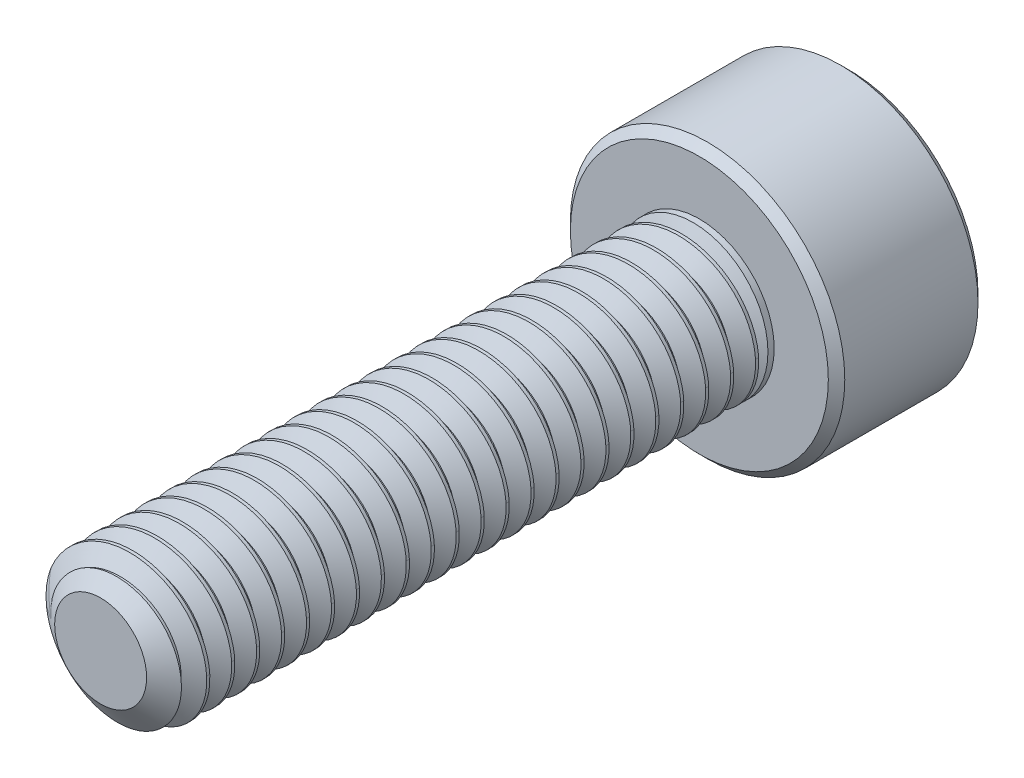
SolidWorks part; units mm, degrees
material "Cast Alloy Steel"
ref_plane "Front Plane" through (0, 0, 0) normal (0, 0, 1) x (1, 0, 0)
ref_plane "Top Plane" through (0, 0, 0) normal (0, 1, 0) x (1, 0, 0)
ref_plane "Right Plane" through (0, 0, 0) normal (1, 0, 0) x (0, 0, -1)
sketch "Sketch1" plane through (0, 0, 0) normal (0, 0, 1) x (1, 0, 0)
  circle A0 centre (0, 0) radius 1.5
  dimension "OD" = 3
extrude "Extrude1" add sketch "Sketch1" against normal blind 12
sketch "Sketch2" plane through (0, 0, 0) normal (0, 0, 1) x (1, 0, 0)
  circle A0 centre (0, 0) radius 1.5 construction
  circle A1 centre (0, 0) radius 1.5
curve "Helix/Spiral1" pitch 0.5 height 12.5 radius 1.5 centre (0, 0, 0) axis (0, 0, -1) start towards (0, 1, 0) parameters "pitch"=0.5
sketch "Sketch3" plane through (0, 0, 0) normal (1, 0, 0) x (0, 0, -1)
  line L0 (-0.4375, 1.5) -> (-0.25, 1.1752)
  line L1 (-0.25, 1.1752) -> (-0.1875, 1.1752)
  line L2 (-0.1875, 1.1752) -> (0, 1.5)
  line L3 (-0.4375, 1.5) -> (0, 1.5)
  line L4 (-0.2187, 1.5) -> (-0.2187, 1.1752) construction
  line L5 (-0.3437, 1.3376) -> (-0.0937, 1.3376) construction
  line L6 (0, 1.5) -> (0, -1.5) construction
  line L7 (0, -1.5) -> (12, -1.5) construction
  point P11 (2.25, -1.5)
  dimension "D1" = 0.0625
  dimension "D2" = 0.25
  dimension "D3" = 60
  dimension "D4" = 2.25
sweep "Cut-Sweep1" cut profiles "Sketch3" path "Helix/Spiral1" align with end faces yes
sketch "Sketch4" plane through (0, 0, 0) normal (1, 0, 0) x (0, 0, -1)
  line L0 (0.4053, 1.5) -> (0, 0.9212)
  line L1 (0, 0.9212) -> (0, 1.5)
  line L2 (0.4053, 1.5) -> (0, 1.5)
  line L3 (-0.4375, 1.5) -> (0, 1.5) construction
  line L4 (0, 0) -> (7.0209, 0) construction
  dimension "D1" = 55
  dimension "D2" = 0.254
revolve "Cut-Revolve1" cut sketch "Sketch4" angle 360 about L4
sketch "Sketch5" plane through (0, 0, 0) normal (1, 0, 0) x (0, 0, -1)
  line L0 (12, -1.1822) -> (12, 1.0703) construction
  line L1 (12, 1.5) -> (0.1203, 1.5)
  line L2 (12, 1.5) -> (12, 0)
  line L3 (12, 0) -> (0.0001, 0)
  line L4 (0.0001, 1.1698) -> (0.0001, 0)
  line L5 (0.1203, 1.5) -> (0.0001, 1.1698)
  line L6 (0, 0) -> (9.9695, 0) construction
  point P3 (0.0001, 1.5)
  point P10 (0.0001, 1.5)
  dimension "D1" = 0.3302
  dimension "Thread min" = 0.0001
  dimension "D3" = 20
revolve "partially thread" [suppressed] add sketch "Sketch5" angle 360 about L6
sketch "Sketch6" plane through (0, 0, -12) normal (0, 0, -1) x (-1, 0, 0)
  circle A0 centre (0, 0) radius 2.75
  dimension "head dia" = 5.5
extrude "Extrude2" add sketch "Sketch6" along normal blind 3
sketch "Sketch7" plane through (0, 0, -15) normal (0, 0, -1) x (-1, 0, 0)
  line L1 (0, 1.4434) -> (-1.25, 0.7217)
  line L2 (-1.25, 0.7217) -> (-1.25, -0.7217)
  line L3 (-1.25, -0.7217) -> (0, -1.4434)
  line L4 (0, -1.4434) -> (1.25, -0.7217)
  line L5 (1.25, -0.7217) -> (1.25, 0.7217)
  line L6 (1.25, 0.7217) -> (0, 1.4434)
  circle A0 centre (0, 0) radius 1.25 construction
  dimension "hex dia" = 2.5
extrude "Cut-Extrude1" cut sketch "Sketch7" against normal blind 1.875
sketch "Sketch8" plane through (0, 0, -15) normal (0, 0, -1) x (-1, 0, 0)
  circle A0 centre (0, 0) radius 1.4434
extrude "Cut-Extrude2" cut sketch "Sketch8" against normal through all draft 45
chamfer "Chamfer1" distance 0.165 angle 45 2 edges at (-2.75, 0, -15) (-2.75, 0, -12)
sketch "Sketch9" plane through (0, 0, 0) normal (1, 0, 0) x (0, 0, -1)
  line L0 (0, 1.5) -> (0, -1.5) construction
  line L1 (2.75, 1.5) -> (2.75, -1.5) construction
  dimension "D1" = 2.75
sketch "Sketch10" plane through (0, 0, 0) normal (1, 0, 0) x (0, 0, -1)
  line L0 (12, 1.5) -> (12, 0)
  line L1 (12, 1.5) -> (11.875, 1.5)
  line L2 (11.875, 1.5) -> (11.2537, 0)
  line L3 (12, 0) -> (11.2537, 0)
  line L4 (12, 2.585) -> (12, -2.585) construction
  dimension "D1" = 22.5
  dimension "D2" = 0.125
revolve "Revolve1" add sketch "Sketch10" angle 360 about L3
equation "\"D3@Helix/Spiral1\" = \"screw length@Extrude1\"+\"pitch@Helix/Spiral1\""
equation "\"D1@Sketch3\" = \"pitch@Helix/Spiral1\"*.125"
equation "\"D2@Sketch3\" = \"pitch@Helix/Spiral1\"*.5"
equation "\"D1@Cut-Extrude1\" = \"hex dia@Sketch7\"*.75"
equation "\"D1@Chamfer1\" = \"head dia@Sketch6\"*.03"
equation "\"D1@Sketch9\" = \"pitch@Helix/Spiral1\"*5.5"
equation "\"D2@Sketch10\" = \"pitch@Helix/Spiral1\"*.25"
equation "\"D4@Sketch3\" = \"pitch@Helix/Spiral1\"*4.50"
